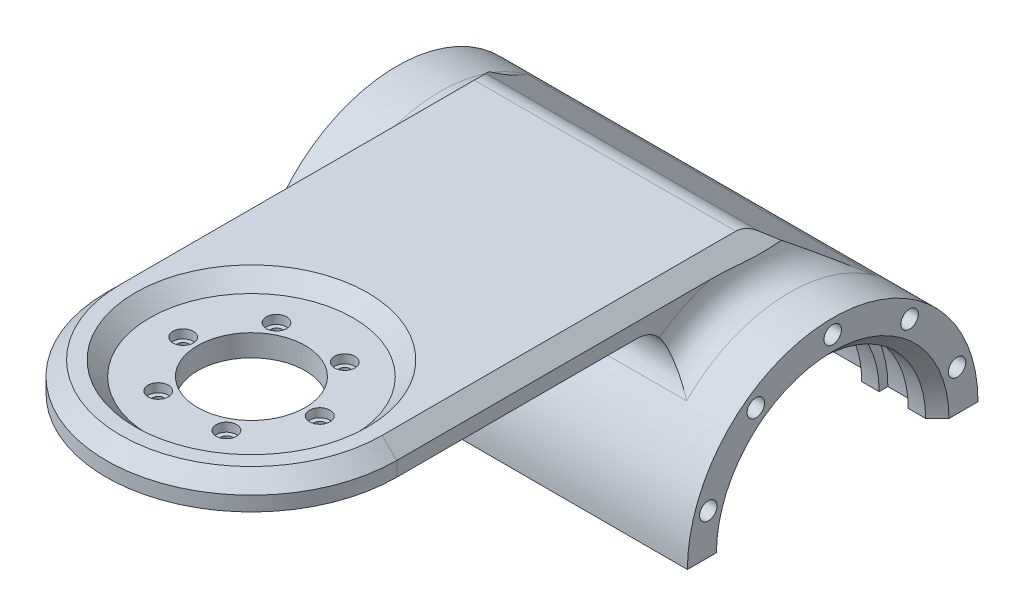
SolidWorks part; units mm, degrees
ref_plane "Front Plane" through (0, 0, 0) normal (0, 0, 1) x (1, 0, 0)
ref_plane "Top Plane" through (0, 0, 0) normal (0, 1, 0) x (1, 0, 0)
ref_plane "Right Plane" through (0, 0, 0) normal (1, 0, 0) x (0, 0, -1)
sketch "Sketch1" plane through (0, 0, 0) normal (0, 1, 0) x (1, 0, 0)
  circle A0 centre (0, 0) radius 23.5
  circle A2 centre (23.5, 0) radius 2
  circle A3 centre (11.75, -20.3516) radius 2
  circle A4 centre (-11.75, -20.3516) radius 2
  circle A5 centre (-23.5, 0) radius 2
  circle A6 centre (-11.75, 20.3516) radius 2
  circle A7 centre (11.75, 20.3516) radius 2
  circle A8 centre (0, 0) radius 27.5
  circle A9 centre (0, 0) radius 18.5
  point P17 (0, 0)
  dimension "D1" = 6
extrude "Boss-Extrude1" add sketch "Sketch1" along normal blind 2.5 contours A7 A0 A6 A5 A4 A3 A2 A9 | A8 A7 A0 A2 A3 A4 A5 A6 region at (20.8365, 0, 0) region at (-26.7222, 0, 0)
sketch "Sketch2" plane through (0, 2.5, 0) normal (0, 1, 0) x (1, 0, 0)
  circle A0 centre (0, 0) radius 50
  circle A1 centre (0, 0) radius 18.5
  circle A2 centre (23.5, 0) radius 2
  circle A3 centre (11.75, -20.3516) radius 2
  circle A4 centre (-11.75, -20.3516) radius 2
  circle A5 centre (-23.5, 0) radius 2
  circle A6 centre (-11.75, 20.3516) radius 2
  circle A7 centre (11.75, 20.3516) radius 2
  point P19 (0, 0)
  dimension "D1" = 6
extrude "Boss-Extrude2" add sketch "Sketch2" along normal blind 10
sketch "Sketch4" plane through (0, 12.5, 0) normal (0, 1, 0) x (1, 0, 0)
  circle A0 centre (0, 0) radius 35
extrude "Cut-Extrude2" cut sketch "Sketch4" against normal blind 5
chamfer "Chamfer2" distance 5 angle 45 1 edges at (0, 12.5, 35)
sketch "Sketch5" plane through (0, 7.5, 0) normal (0, 1, 0) x (1, 0, 0)
  circle A0 centre (-23.5, 0) radius 3.5
  circle A1 centre (-11.75, 20.3516) radius 3.5
  circle A2 centre (11.75, 20.3516) radius 3.5
  circle A3 centre (23.5, 0) radius 3.5
  circle A4 centre (11.75, -20.3516) radius 3.5
  circle A5 centre (-11.75, -20.3516) radius 3.5
  point P15 (0, 0)
  dimension "D1" = 6
extrude "Cut-Extrude3" cut sketch "Sketch5" against normal blind 3
sketch "Sketch6" plane through (0, 12.5, 0) normal (0, 1, 0) x (1, 0, 0)
  line L0 (-50, 0) -> (-50, 90)
  line L1 (50, 0) -> (50, 90)
  line L2 (50, 90) -> (-50, 90)
  line L3 (-50, 90) -> (-50, 125)
  line L4 (-50, 125) -> (50, 125)
  line L5 (50, 125) -> (50, 90)
  circle A0 centre (0, 0) radius 50 construction
  circle M4 centre (0, 0) radius 50
sketch "Sketch7" plane through (0, 0, 0) normal (1, 0, 0) x (0, 0, -1)
  line L0 (0, 0) -> (75, 0)
  line L1 (75, 0) -> (75, 12.5)
  line L2 (0, 12.5) -> (90, 12.5) construction
  line L3 (0, 0) -> (0, -50)
  line L4 (0, -50) -> (75, -50)
  line L5 (75, -50) -> (75, 0)
  line L6 (75, -50) -> (125, -50)
  circle A0 centre (125, -50) radius 50
  circle A1 centre (125, -50) radius 40
extrude "Boss-Extrude3" add sketch "Sketch7" along normal blind 75 and the other way blind 75 separate body contours A1 A0 region at (0, -1.4142, -125)
extrude "Boss-Extrude4" add sketch "Sketch6" against normal blind 10 contours L1 L2 L0 M4 | L5 L4 L3 L2 region at (0, 12.5, -63.4075) region at (0, 12.5, -107.5)
sketch "Sketch11" plane through (75, 0, 0) normal (1, 0, 0) x (0, 0, -1)
  line L0 (125, 12.5) -> (125, -50)
  line L1 (125, 12.5) -> (155, -10)
  line L2 (125, 2.5) -> (128.4965, -0.1224)
  line L3 (125, 2.5) -> (121.5035, -0.1224)
  line L4 (125, 12.5) -> (95, -10)
  circle A0 centre (125, -50) radius 50 construction
  circle M2 centre (125, -50) radius 50
extrude "Boss-Extrude6" add sketch "Sketch11" against normal blind 100 from offset 25 contours L0 L2 L1 M2 | L0 L4 L3 M2 | L0 L3 M2 | L2 L0 M2 region at (75, 2.8846, -133.0474) region at (75, 2.8846, -116.9526) region at (75, 0.8065, -126.1558) region at (75, 0.8065, -123.8442) offset against normal yes
sketch "Sketch12" plane through (75, 0, 0) normal (1, 0, 0) x (0, 0, -1)
  line L1 (175, -50) -> (75, -50)
  circle A1 centre (125, -50) radius 50 construction
  circle A2 centre (125, -50) radius 50
  circle M8 centre (125, -50) radius 50
  circle M9 centre (125, -50) radius 40
extrude "Cut-Extrude5" cut sketch "Sketch12" against normal blind 150 contours L1 M8 M9 region at (75, -98.882, -125)
chamfer "Chamfer3" distance 5 angle 45 3 edges at (-50, 12.5, -62.5) (0, 12.5, 50) (50, 12.5, -62.5)
fillet "Fillet3" radius 10 2 edges at (0, 12.5, -125) (0, 2.5, -111.6667)
fillet "Fillet4" radius 10 2 edges at (-50, -0.1227, -121.4988) (50, -0.1227, -121.4988)
sketch "Sketch13" plane through (0, 12.5, 0) normal (0, 1, 0) x (1, 0, 0)
  line L0 (-60, 155) -> (-60, 175)
  line L1 (-75, 175) -> (75, 175) construction
  line L2 (60, 155) -> (60, 175)
  line L3 (60, 175) -> (-60, 175)
  circle A0 centre (-60, 175) radius 2.5
  circle A1 centre (0, 175) radius 2.5
  circle A2 centre (60, 175) radius 2.5
  circle A3 centre (-60, 175) radius 4.25
  circle A4 centre (0, 175) radius 4.25
  circle A5 centre (60, 175) radius 4.25
  dimension "D1" = 3
extrude "Boss-Extrude7" add sketch "Sketch13" against normal blind 12.5 from offset 50 separate body contours A2 | A1 | A0 | A3 | A4 | A5 offset against normal yes
combine bodies "Combine1" operation type add bodies to combine 117 116 115 111
sketch "Sketch14" plane through (0, -50, 0) normal (0, -1, 0) x (1, 0, 0)
  line L0 (-62.5, -175) -> (-57.5, -175) construction
  line L1 (-2.5, -175) -> (2.5, -175) construction
  line L2 (57.5, -175) -> (62.5, -175) construction
  circle A0 centre (-60, -175) radius 2.5
  circle A1 centre (0, -175) radius 2.5
  circle A2 centre (60, -175) radius 2.5
  circle A3 centre (-60, -175) radius 4
  circle A4 centre (0, -175) radius 4
  circle A5 centre (60, -175) radius 4
  arc M1 (62.5, -175) -> (57.5, -175) centre (60, -175) cw
  line M2 (57.5, -175) -> (62.5, -175)
  line M14 (-2.5, -175) -> (2.5, -175)
  line M16 (-62.5, -175) -> (-57.5, -175)
extrude "Cut-Extrude6" cut sketch "Sketch14" against normal blind 100 contours M1 M2 | A1 M14 | A0 M16 | A2 M2 region at (-60, -50, -173.939) region at (0, -50, -173.939) region at (60, -50, -173.939) region at (60, -50, -176.061)
sketch "Sketch15" plane through (0, -37.5, 0) normal (0, 1, 0) x (1, 0, 0)
  circle A0 centre (-60, 175) radius 4.25
  circle A1 centre (0, 175) radius 4.25
  circle A2 centre (60, 175) radius 4.25
extrude "Cut-Extrude7" cut sketch "Sketch15" along normal blind 100
sketch "Sketch16" plane through (75, 0, 0) normal (1, 0, 0) x (0, 0, -1)
  line L0 (161, -50) -> (165, -50)
  line L1 (85, -50) -> (89, -50)
  circle A0 centre (125, -50) radius 40
  circle A1 centre (125, -50) radius 36
  arc M4 (85, -50) -> (165, -50) centre (125, -50) cw
extrude "Boss-Extrude8" add sketch "Sketch16" against normal blind 5 from offset 5 contours A1 L0 L1 M4 region at (75, -13.1056, -125) offset against normal yes
sketch "Sketch18" plane through (75, 0, 0) normal (1, 0, 0) x (0, 0, -1)
  line L0 (85, -50) -> (89, -50)
  line L1 (161, -50) -> (165, -50)
  circle A0 centre (125, -50) radius 36
  circle A1 centre (125, -50) radius 40
  arc M3 (85, -50) -> (165, -50) centre (125, -50) cw
extrude "Boss-Extrude9" add sketch "Sketch18" against normal blind 5 from offset 20 contours A0 L1 L0 M3 region at (75, -10.8944, -125) offset against normal yes
ref_plane "Plane1" through (0, 0, 0) normal (1, 0, 0) x (0, 0, -1)
sketch "Sketch19" plane through (75, 0, 0) normal (1, 0, 0) x (0, 0, -1)
  line L0 (85, -50) -> (165, -50)
  circle A0 centre (125, -50) radius 39
  circle A1 centre (125, -50) radius 40
  arc M3 (85, -50) -> (165, -50) centre (125, -50) cw
extrude "Boss-Extrude10" add sketch "Sketch19" against normal blind 20 from offset 5 contours A0 L0 M3 region at (75, -10.1056, -125) offset against normal yes
mirror "Mirror1" about plane through (0, 0, 0) normal (1, 0, 0) of "Boss-Extrude10", "Boss-Extrude9", "Boss-Extrude8"
chamfer "Chamfer4" distance 5 angle 45 4 edges at (-50, -10, -125) (-70, -10, -125) (50, -10, -125) (70, -10, -125)
sketch "Sketch20" plane through (-75, 0, 0) normal (-1, 0, 0) x (0, 0, 1)
  line L0 (-175, -50) -> (-75, -50)
  line L2 (-125, 0) -> (-125, -10)
  arc A0 (-75, -50) -> (-175, -50) centre (-125, -50) ccw construction
  arc A1 (-85, -50) -> (-165, -50) centre (-125, -50) ccw construction
  circle A2 centre (-125, -5) radius 3
  circle A3 centre (-98.5497, -13.5942) radius 3
  circle A4 centre (-82.2025, -36.0942) radius 3
  circle A5 centre (-82.2025, -63.9058) radius 3 [skipped]
  circle A6 centre (-98.5497, -86.4058) radius 3 [skipped]
  circle A7 centre (-125, -95) radius 3 [skipped]
  circle A8 centre (-151.4503, -86.4058) radius 3 [skipped]
  circle A9 centre (-167.7975, -63.9058) radius 3
  circle A10 centre (-167.7975, -36.0942) radius 3
  circle A11 centre (-151.4503, -13.5942) radius 3
  point P33 (-125, -50)
  dimension "D1" = 10
extrude "Cut-Extrude8" cut sketch "Sketch20" against normal blind 5 contours A2 | A3 | A4 | A10 | A11
mirror "Mirror2" about plane through (0, 0, 0) normal (1, 0, 0) of "Cut-Extrude8"
